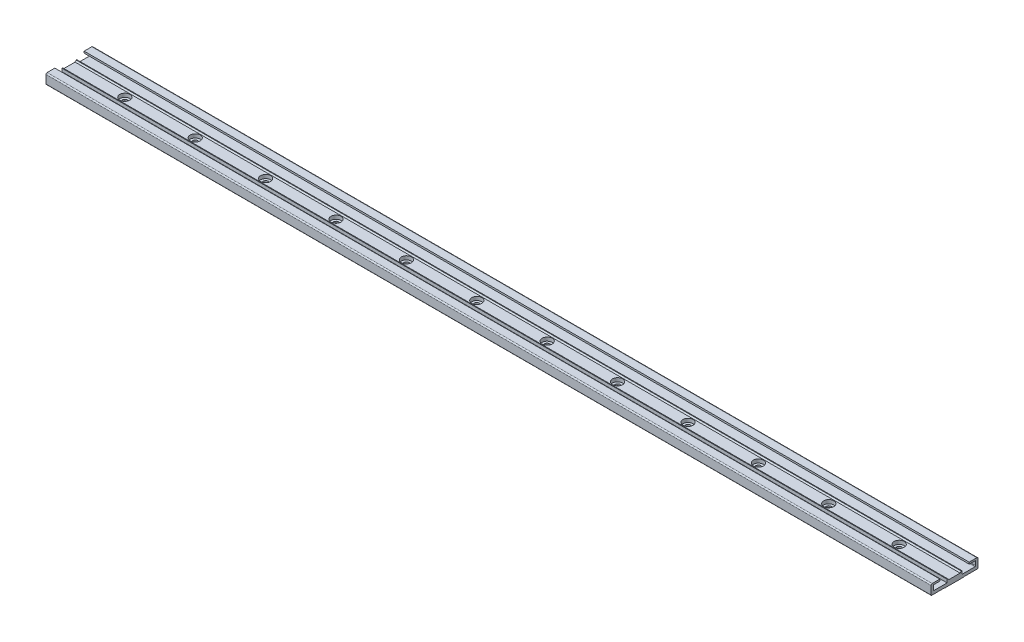
SolidWorks part; units mm, degrees
material "6061-T6 (SS)"
ref_plane "Front" through (0, 0, 0) normal (0, 0, 1) x (1, 0, 0)
ref_plane "Top" through (0, 0, 0) normal (0, 1, 0) x (1, 0, 0)
ref_plane "Right" through (0, 0, 0) normal (1, 0, 0) x (0, 0, -1)
sketch "Sketch1" plane through (0, 0, 0) normal (1, 0, 0) x (0, 0, -1)
  line L0 (-8, 0.2) -> (-8, 0)
  line L1 (-8, 0) -> (8, 0)
  line L2 (8, 0) -> (8, 0.2)
  line L3 (8, 0.2) -> (19.5, 0.2)
  line L4 (20, 0.7) -> (20, 7.7)
  line L5 (19, 8.7) -> (12.5, 8.7)
  line L6 (12.5, 8.7) -> (12.5, 7.2)
  line L7 (12.5, 7.2) -> (17.5, 7.2)
  line L8 (18, 6.7) -> (18, 3.3)
  line L9 (17.5, 2.8) -> (6.3, 2.8)
  line L10 (6.3, 2.8) -> (6.3, 5.5)
  line L11 (6.3, 5.5) -> (5.75, 5.5)
  line L12 (5.75, 5.5) -> (4.75, 4.5)
  line L13 (4.75, 4.5) -> (-4.75, 4.5)
  line L14 (-4.75, 4.5) -> (-5.75, 5.5)
  line L15 (-5.75, 5.5) -> (-6.3, 5.5)
  line L16 (-6.3, 5.5) -> (-6.3, 2.8)
  line L17 (-6.3, 2.8) -> (-17.5, 2.8)
  line L18 (-18, 3.3) -> (-18, 6.7)
  line L19 (-17.5, 7.2) -> (-12.5, 7.2)
  line L20 (-12.5, 7.2) -> (-12.5, 8.7)
  line L21 (-12.5, 8.7) -> (-19, 8.7)
  line L22 (-20, 7.7) -> (-20, 0.7)
  line L23 (-19.5, 0.2) -> (-8, 0.2)
  arc A0 (19.5, 0.2) -> (20, 0.7) centre (19.5, 0.7) ccw
  arc A1 (20, 7.7) -> (19, 8.7) centre (19, 7.7) ccw
  arc A2 (18, 6.7) -> (17.5, 7.2) centre (17.5, 6.7) ccw
  arc A3 (17.5, 2.8) -> (18, 3.3) centre (17.5, 3.3) ccw
  arc A4 (-18, 3.3) -> (-17.5, 2.8) centre (-17.5, 3.3) ccw
  arc A5 (-17.5, 7.2) -> (-18, 6.7) centre (-17.5, 6.7) ccw
  arc A6 (-19, 8.7) -> (-20, 7.7) centre (-19, 7.7) ccw
  arc A7 (-20, 0.7) -> (-19.5, 0.2) centre (-19.5, 0.7) ccw
extrude "Boss-Extrude1" add sketch "Sketch1" along normal blind 754.38
hole_wizard "CBORE for M4 SBHCS1" positions "Sketch2" profile "Sketch3" counterbore size "M4" standard "ANSI Metric" end condition through all
sketch "Sketch2" plane through (0, 4.5, 0) normal (0, 1, 0) x (1, 0, 0)
  line L1 (47.19, 0) -> (0, 0) construction
  line L3 (754.38, 0) -> (707.19, 0) construction
  line L4 (754.38, 4.75) -> (754.38, -4.75) construction
  point P0 (47.19, 0)
  dimension "D1" = 660
sketch "Sketch3" plane through (47.19, 4.5, 0) normal (1, 0, 0) x (0, 0, 1)
  line L0 (0, 0) -> (0, 4.5)
  line L1 (0, 4.5) -> (2.25, 4.5)
  line L3 (2.25, 4.5) -> (2.25, 3.1)
  line L4 (2.25, 3.1) -> (4.3, 3.1)
  line L5 (4.3, 3.1) -> (4.3, 0)
  line L7 (4.3, 0) -> (0, 0)
  line L11 (0, -6.35) -> (0, 107.95) construction
  dimension "Thru Hole Dia." = 4.5
  dimension "Thru Hole Depth" = 4.5
  dimension "C'Bore Dia." = 8.6
  dimension "C'Bore Depth" = 3.1
pattern_linear "LPattern1" count 12 spacing 60 along (1, 0, 0) of "CBORE for M4 SBHCS1"
equation "\"END\"= int ( \"RD1@Annotations\" / 60 )"
equation "\"D1@Sketch2\"=(\"END\"-1)*60"
